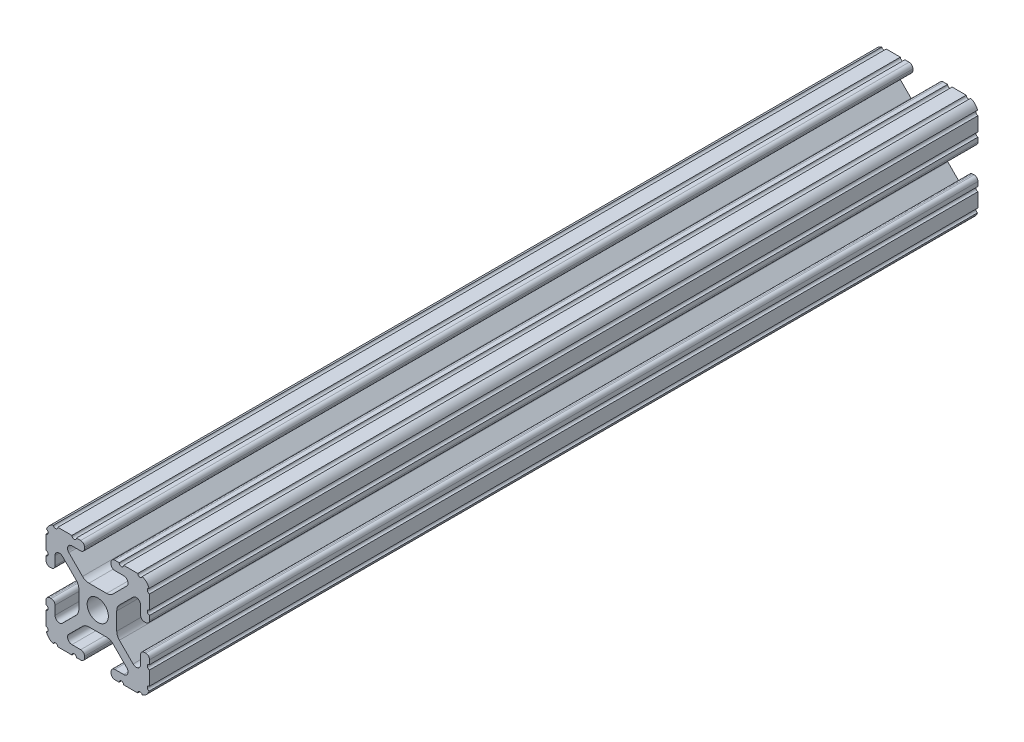
SolidWorks part; units mm, degrees
ref_plane "Front Plane" through (0, 0, 0) normal (0, 0, 1) x (1, 0, 0)
ref_plane "Top Plane" through (0, 0, 0) normal (0, 1, 0) x (1, 0, 0)
ref_plane "Right Plane" through (0, 0, 0) normal (1, 0, 0) x (0, 0, -1)
sketch "Sketch2" plane through (0, 0, 0) normal (0, 0, 1) x (1, 0, 0)
  line L0 (0, 12.7) -> (0, -12.7) construction
  line L1 (-12.7, 0) -> (12.7, 0) construction
  line L2 (3.2512, -12.7) -> (12.7, -12.7)
  line L3 (12.7, -12.7) -> (12.7, -3.2512)
  line L4 (3.2512, -12.7) -> (3.2512, -10.4902)
  line L5 (3.2512, -10.4902) -> (8.9276, -10.4902)
  line L6 (8.9276, -10.4902) -> (3.0856, -4.6482)
  line L7 (0, 0) -> (12.7, -12.7) construction
  line L8 (12.7, -3.2512) -> (10.4902, -3.2512)
  line L9 (10.4902, -3.2512) -> (10.4902, -8.9276)
  line L10 (10.4902, -8.9276) -> (4.6482, -3.0856)
  circle A0 centre (0, 0) radius 2.6035
  arc A1 (6.3485, -10.4902) -> (7.1039, -8.6665) centre (6.3485, -9.4219) ccw construction
  point P8 (0, -4.6482)
  dimension "Center Hole Diameter" = 5.207
  dimension "Rail Height" = 25.4
  dimension "Rail Width" = 25.4
  dimension "T-Slot Width" = 6.5024
  dimension "Slot Inner Width" = 14.8336
  dimension "Thickness" = 2.2098
  dimension "Slot Depth" = 5.842
  dimension "D1" = 2.2098
sketch "Sketch3" plane through (0, 0, 0) normal (1, 0, 0) x (0, 0, -1)
  line L0 (-101.6, -12.7) -> (101.6, -12.7) construction
  line L1 (-76.2, 0) -> (76.2, 0) construction
  dimension "Length" = 203.2
sketch "Sketch4" plane through (0, 0, 0) normal (0, 0, 1) x (1, 0, 0)
  line L0 (4.1904, -12.7) -> (10.1173, -12.7)
  line L1 (3.2512, -12.7) -> (12.7, -12.7) construction
  line L2 (3.2512, -12.7) -> (3.2512, -10.4902) construction
  line L3 (3.2512, -10.4902) -> (8.9276, -10.4902) construction
  line L4 (3.2512, -11.4294) -> (3.2512, -11.7608)
  line L5 (4.1904, -10.4902) -> (6.3485, -10.4902)
  line L6 (0, -4.6482) -> (2.164, -4.6482)
  line L7 (8.9276, -10.4902) -> (3.0856, -4.6482) construction
  line L8 (3.7373, -5.2999) -> (7.1039, -8.6665)
  line L9 (12.7, -12.7) -> (12.7, -3.2512) construction
  line L10 (10.4902, -8.9276) -> (4.6482, -3.0856) construction
  line L11 (10.4902, -3.2512) -> (10.4902, -8.9276) construction
  line L12 (10.4902, -6.3485) -> (10.4902, -4.1904)
  line L13 (12.7, -3.2512) -> (10.4902, -3.2512) construction
  line L14 (11.4294, -3.2512) -> (11.7608, -3.2512)
  line L15 (12.7, -4.1904) -> (12.7, -10.1173)
  line L16 (8.6665, -7.1039) -> (5.2999, -3.7373)
  line L17 (4.6482, 0) -> (4.6482, -2.164)
  line L18 (-12.7, 0) -> (12.7, 0) construction
  line L19 (0, -4.6482) -> (0, -2.6035)
  line L20 (0, 12.7) -> (0, -12.7) construction
  line L21 (4.6482, 0) -> (2.6035, 0)
  arc A0 (3.2512, -11.7608) -> (4.1904, -12.7) centre (4.1904, -11.7608) ccw
  arc A2 (3.2512, -11.4294) -> (4.1904, -10.4902) centre (4.1904, -11.4294) cw
  arc A3 (6.3485, -10.4902) -> (7.1039, -8.6665) centre (6.3485, -9.4219) ccw
  arc A4 (2.164, -4.6482) -> (3.7373, -5.2999) centre (2.164, -6.8732) cw
  arc A5 (10.1173, -12.7) -> (12.7, -10.1173) centre (10.1173, -10.1173) ccw
  arc A6 (8.6665, -7.1039) -> (10.4902, -6.3485) centre (9.4219, -6.3485) ccw
  arc A7 (10.4902, -4.1904) -> (11.4294, -3.2512) centre (11.4294, -4.1904) cw
  arc A8 (11.7608, -3.2512) -> (12.7, -4.1904) centre (11.7608, -4.1904) cw
  arc A9 (5.2999, -3.7373) -> (4.6482, -2.164) centre (6.8732, -2.164) cw
  circle A10 centre (0, 0) radius 2.6035 construction
  arc A11 (0, -2.6035) -> (2.6035, 0) centre (0, 0) ccw
  dimension "D1" = 2.5827
  dimension "D2" = 2.225
  dimension "D3" = 0.9392
extrude "Boss-Extrude1" add sketch "Sketch4" along normal mid plane 203.2
sketch "Sketch5" plane through (0, 0, 0) normal (0, 0, 1) x (1, 0, 0)
  line L0 (3.2512, -12.7) -> (12.7, -12.7) construction
  line L1 (4.1904, -10.4902) -> (6.3485, -10.4902) construction
  line L3 (0, 0) -> (12.7, -12.7) construction
  line L4 (6.3485, -10.4902) -> (6.3485, -12.7) construction
  line L5 (8.9276, -10.4902) -> (3.0856, -4.6482) construction
  circle A0 centre (10.3562, -12.7) radius 0.5524
  circle A1 centre (5.796, -12.7) radius 0.5524
  circle A2 centre (12.7, -10.3562) radius 0.5524
  circle A3 centre (12.7, -5.796) radius 0.5524
  point P10 (5.2694, -10.4902)
  point P12 (9.4219, -6.3485)
  dimension "D1" = 1.1049
extrude "Cut-Extrude1" cut sketch "Sketch5" against normal through all both and the other way through all
mirror "Mirror1" about plane through (0, 0, 0) normal (1, 0, 0) of bodies 137 134
mirror "Mirror2" about plane through (0, 0, 0) normal (0, 1, 0) of bodies 135
equation "\"D1@Boss-Extrude1\"=\"Length@Sketch3\""
equation "\"D1@Sketch2\"=\"Thickness@Sketch2\""
equation "\"D2@Sketch4\"=\"Slot Inner Width@Sketch2\"*0.15"
equation "\"D1@Sketch4\"=\"D3@Sketch4\"*2.75"
equation "\"D3@Sketch4\"=\"Thickness@Sketch2\"*0.425"
equation "\"D1@Sketch5\"=\"Thickness@Sketch2\"*0.5"
